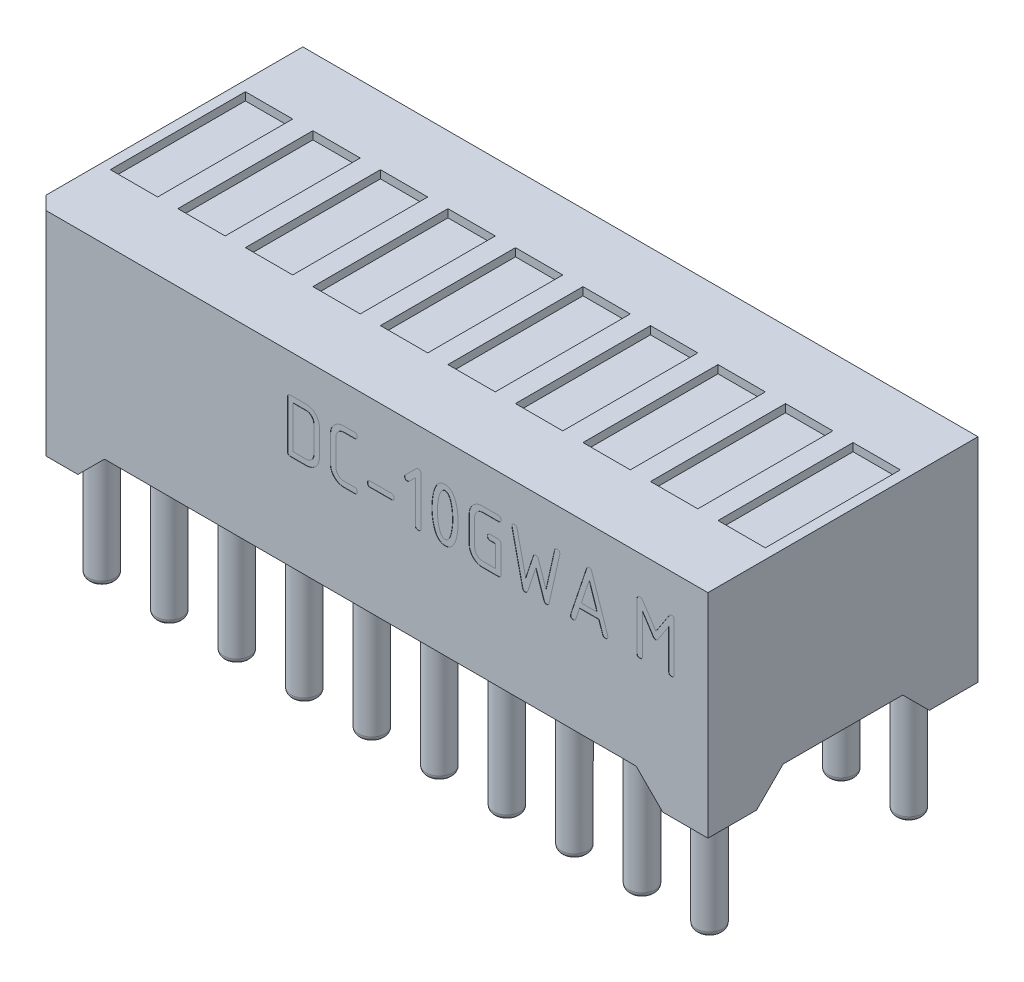
SolidWorks part; units mm, degrees
material "ABS"
ref_plane "Спереди" through (0, 0, 0) normal (0, 0, 1) x (1, 0, 0)
ref_plane "Сверху" through (0, 0, 0) normal (0, 1, 0) x (1, 0, 0)
ref_plane "Справа" through (0, 0, 0) normal (1, 0, 0) x (0, 0, -1)
sketch "Эскиз1" plane through (0, 0, 0) normal (0, 1, 0) x (1, 0, 0)
  line L1 (12.7, 5.08) -> (-12.7, 5.08)
  line L2 (12.7, 5.08) -> (12.7, -5.08)
  line L3 (12.7, -5.08) -> (-12.7, -5.08)
  line L4 (-12.7, 5.08) -> (-12.7, -5.08)
  line L5 (12.7, 5.08) -> (-12.7, -5.08) construction
  line L6 (12.7, -5.08) -> (-12.7, 5.08) construction
  point P0 (0, 0)
  dimension "D1" = 25.4
  dimension "D2" = 10.16
extrude "Бобышка-Вытянуть1" add sketch "Эскиз1" along normal blind 8
sketch "Эскиз2" plane through (12.7, 0, 0) normal (1, 0, 0) x (0, 0, -1)
  line L1 (-5.08, 0) -> (5.08, 0) construction
  line L2 (2.25, 1) -> (-2.25, 1)
  line L3 (2.25, 1) -> (2.25, -1)
  line L4 (2.25, -1) -> (-2.25, -1)
  line L5 (-2.25, 1) -> (-2.25, -1)
  line L6 (2.25, 1) -> (-2.25, -1) construction
  line L7 (2.25, -1) -> (-2.25, 1) construction
  point P0 (0, 0)
  dimension "D1" = 2
  dimension "D2" = 4.5
extrude "Вырез-Вытянуть1" cut sketch "Эскиз2" against normal through all
chamfer "Фаска1" distance 1 angle 45 2 edges at (0, 0, -2.25) (0, 0, 2.25)
sketch "Эскиз3" plane through (0, 0, -5.08) normal (0, 0, -1) x (-1, 0, 0)
  line L1 (-12.7, 0) -> (12.7, 0) construction
  line L2 (10, 1) -> (-10, 1)
  line L3 (10, 1) -> (10, -1)
  line L4 (10, -1) -> (-10, -1)
  line L5 (-10, 1) -> (-10, -1)
  line L6 (10, 1) -> (-10, -1) construction
  line L7 (10, -1) -> (-10, 1) construction
  point P0 (0, 0)
  dimension "D1" = 2
  dimension "D2" = 20
extrude "Вырез-Вытянуть2" cut sketch "Эскиз3" against normal through all
chamfer "Фаска2" distance 1 angle 45 4 edges at (-10, 0, 4.165) (10, 0, 4.165) (-10, 0, -4.165) (10, 0, -4.165)
sketch "Эскиз4" plane through (0, 8, 0) normal (0, 1, 0) x (1, 0, 0)
  line L0 (12.7, 0) -> (-12.7, 0) construction
  line L1 (12.7, -5.08) -> (12.7, 5.08) construction
  line L2 (-12.7, 5.08) -> (-12.7, -5.08) construction
  line L4 (0.38, -2.54) -> (2.16, -2.54)
  line L5 (0.38, -2.54) -> (0.38, 2.54)
  line L6 (0.38, 2.54) -> (2.16, 2.54)
  line L7 (2.16, -2.54) -> (2.16, 2.54)
  line L8 (0.38, -2.54) -> (2.16, 2.54) construction
  line L9 (0.38, 2.54) -> (2.16, -2.54) construction
  point P6 (1.27, 0)
  point P11 (0, 0)
  dimension "D1" = 5.08
  dimension "D2" = 1.78
  dimension "D3" = 1.27
extrude "Вырез-Вытянуть3" cut sketch "Эскиз4" against normal blind 0.3
pattern_linear "Линейный массив1" count 6 spacing 2.54 along (-1, 0, 0) count 5 spacing 2.54 along (1, 0, 0) of "Вырез-Вытянуть3"
sketch "Эскиз5" plane through (0, 1, 0) normal (0, -1, 0) x (1, 0, 0)
  line L0 (0, 0) -> (-1.27, 0) construction
  line L1 (-1.27, 3.75) -> (-1.27, -3.75) construction
  circle A0 centre (-1.27, 3.75) radius 0.5
  circle A1 centre (-1.27, -3.75) radius 0.5
  dimension "D1" = 1
  dimension "D2" = 1.27
  dimension "D3" = 7.5
extrude "Бобышка-Вытянуть2" add sketch "Эскиз5" along normal blind 5.2
pattern_linear "Линейный массив2" count 6 spacing 2.54 along (1, 0, 0) count 5 spacing 2.54 along (-1, 0, 0) of "Бобышка-Вытянуть2"
fillet "Скругление1" radius 0.2 20 edges at (3.81, -4.2, 3.25) (6.35, -4.2, 3.25) (8.89, -4.2, 3.25) (11.43, -4.2, 3.25) (11.43, -4.2, -4.25) (8.89, -4.2, -4.25) (6.35, -4.2, -4.25) (3.81, -4.2, -4.25) (1.27, -4.2, -4.25) (-1.27, -4.2, -4.25) (-3.81, -4.2, -4.25) (-6.35, -4.2, -4.25) (-8.89, -4.2, -4.25) (-11.43, -4.2, -4.25) (-11.43, -4.2, 3.25) (-8.89, -4.2, 3.25) (-6.35, -4.2, 3.25) (-3.81, -4.2, 3.25) (-1.27, -4.2, 3.25) (1.27, -4.2, 3.25)
chamfer "Фаска3" distance 0.5 angle 45 1 edges at (-12.7, 4, 5.08)
sketch "Эскиз6" plane through (0, 0, 5.08) normal (0, 0, 1) x (1, 0, 0)
  text T0 "DC-10GWA M" font "GOST Common" height 2
extrude "Вырез-Вытянуть4" cut sketch "Эскиз6" against normal blind 0.01
